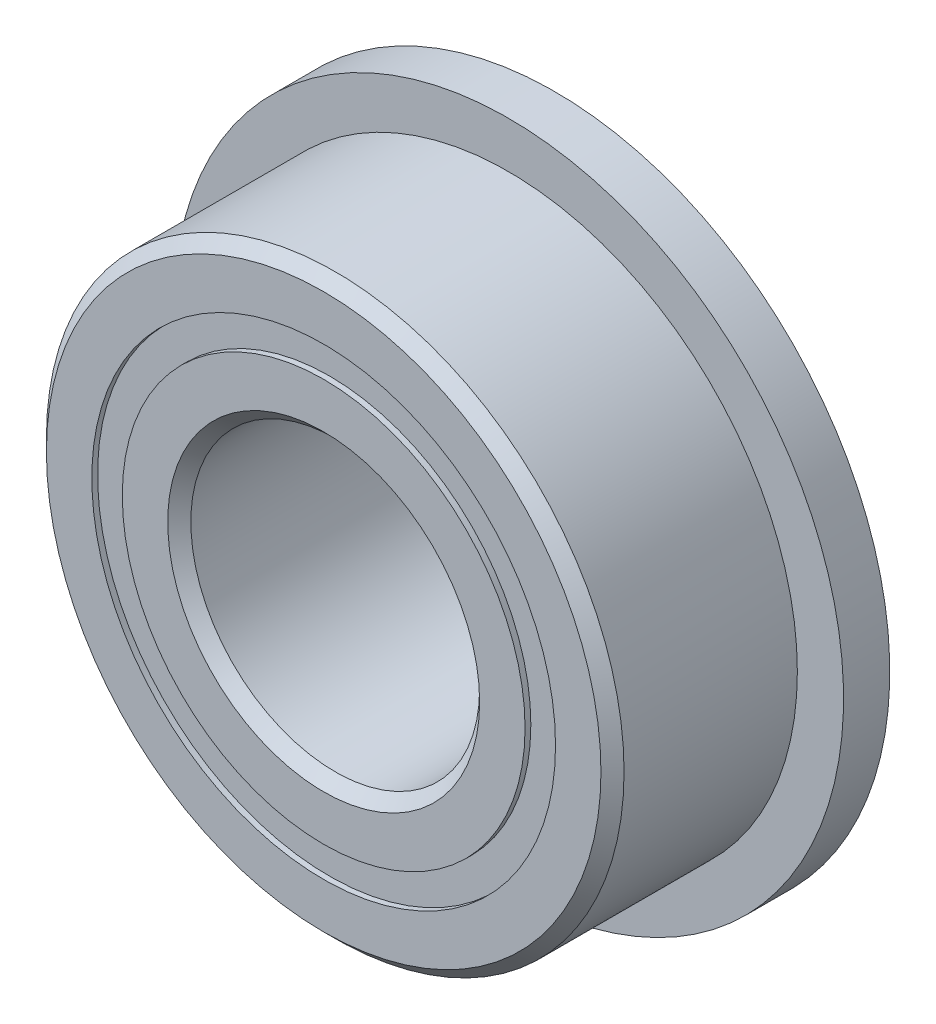
SolidWorks part; units mm, degrees
ref_plane "Front Plane" through (0, 0, 0) normal (0, 0, 1) x (1, 0, 0)
ref_plane "Top Plane" through (0, 0, 0) normal (0, 1, 0) x (1, 0, 0)
ref_plane "Right Plane" through (0, 0, 0) normal (1, 0, 0) x (0, 0, -1)
sketch "Sketch1" plane through (0, 0, 0) normal (1, 0, 0) x (0, 0, -1)
  line L0 (-2, 0) -> (2, 0) construction
  line L1 (0, 5) -> (0, -5) construction
  line L2 (1.8, 5) -> (-1.8, 5)
  line L3 (-1.8, 5) -> (-2, 4.8)
  line L4 (-2, 4.8) -> (-2, 4.0137)
  line L5 (-2, 4.0137) -> (-0.8889, 4.0137)
  line L6 (2, 4.0137) -> (0.8889, 4.0137)
  line L7 (2, 4.8) -> (2, 4.0137)
  line L8 (1.8, 5) -> (2, 4.8)
  line L9 (0, 5) -> (0, 3.75) construction
  line L10 (0, 3.75) -> (0, 2.5) construction
  arc A0 (-0.8889, 4.0137) -> (0.8889, 4.0137) centre (0, 3.75) cw
  point P14 (0, 2.5)
  dimension "Width" = 4
  dimension "OD" = 10
  dimension "D1" = 45
  dimension "D2" = 0.2
  dimension "Shaft Dia" = 5
  dimension "D3" = 1.7778
  dimension "D4" = 0.2637
revolve "Revolve1" add sketch "Sketch1" angle 360 about L0
sketch "Sketch3" plane through (0, 0, 0) normal (1, 0, 0) x (0, 0, -1)
  line L0 (-2, 3.4863) -> (-0.8889, 3.4863)
  line L1 (0, 5) -> (0, -5) construction
  line L2 (-2, 4.8) -> (-2, 4.0137) construction
  line L3 (-2, 3.4863) -> (-2, 2.7)
  line L4 (-1.8, 5) -> (-2, 4.8) construction
  line L5 (-2, 2.7) -> (-1.8, 2.5)
  line L6 (-1.8, 2.5) -> (1.8, 2.5)
  line L7 (1.8, 5) -> (1.8, -5) construction
  line L8 (1.8, 2.5) -> (2, 2.7)
  line L9 (2, -4.8) -> (2, 4.8) construction
  line L10 (2, 2.7) -> (2, 3.4863)
  line L11 (2, 3.4863) -> (0.8889, 3.4863)
  line L13 (1.8, 5) -> (2, 4.8) construction
  arc A0 (0.8889, 4.0137) -> (-0.8889, 4.0137) centre (0, 3.75) ccw construction
  arc A1 (0.8889, 3.4863) -> (-0.8889, 3.4863) centre (0, 3.75) cw
revolve "Revolve3" add sketch "Sketch3" angle 360 about L0
sketch "Sketch4" plane through (0, 0, 0) normal (1, 0, 0) x (0, 0, -1)
  line L0 (-0.9272, 3.75) -> (0.9272, 3.75)
  arc A2 (-0.9272, 3.75) -> (0.9272, 3.75) centre (0, 3.75) cw
  arc A3 (0.8889, 4.0137) -> (-0.8889, 4.0137) centre (0, 3.75) ccw construction
revolve "Revolve4" add sketch "Sketch4" angle 360 about L0
ref_axis "Axis1" through (0, 0, -2) along (0, 0, 1)
pattern_circular "CirPattern1" count 12 every 30 about axis through (0, 0, -2) along (0, 0, 1) of bodies 104
sketch "Sketch5" plane through (0, 0, 0) normal (1, 0, 0) x (0, 0, -1)
  line L0 (-2, 4.0137) -> (-0.8889, 4.0137) construction
  line L1 (-1.9, 4.0137) -> (-0.9272, 4.0137)
  line L2 (-1.9, 4.0137) -> (-1.9, 3.4863)
  line L3 (-1.9, 3.4863) -> (-0.9272, 3.4863)
  line L4 (-0.9272, 4.0137) -> (-0.9272, 3.4863)
  line L5 (-2, 3.4863) -> (-0.8889, 3.4863) construction
  line L6 (2, 4.0137) -> (0.8889, 4.0137) construction
  line L7 (1.9, 4.0137) -> (0.9272, 4.0137)
  line L8 (1.9, 4.0137) -> (1.9, 3.4863)
  line L9 (1.9, 3.4863) -> (0.9272, 3.4863)
  line L10 (0.9272, 4.0137) -> (0.9272, 3.4863)
  line L11 (2, 3.4863) -> (0.8889, 3.4863) construction
  line L12 (-1.8, 5) -> (-2, 4.8) construction
  point P18 (-1.9, 4.9)
revolve "Revolve5" add sketch "Sketch5" angle 360 about L0
sketch "Sketch6" plane through (0, 0, 0) normal (1, 0, 0) x (0, 0, -1)
  line L0 (2, 0) -> (-2, 0) construction
  line L1 (2, 4.0137) -> (1.2, 4.0137)
  line L2 (2, 4.0137) -> (2, 5.8)
  line L3 (2, 5.8) -> (1.2, 5.8)
  line L4 (1.2, 4.0137) -> (1.2, 5.8)
  dimension "Th" = 0.8
  dimension "Flange OD" = 11.6
revolve "Revolve6" add sketch "Sketch6" angle 360 about L0
equation "\"D2@Sketch1\" = \"Width@Sketch1\"*.05"
equation "\"D3@Sketch1\" = \"Width@Sketch1\"/2.25"
equation "\"D4@Sketch1\" = (((\"OD@Sketch1\"-\"Width@Sketch1\")/2)/3.25)/3.5"
equation "\"D2@CirPattern1\" = 360/\"Balls@CirPattern1\""
